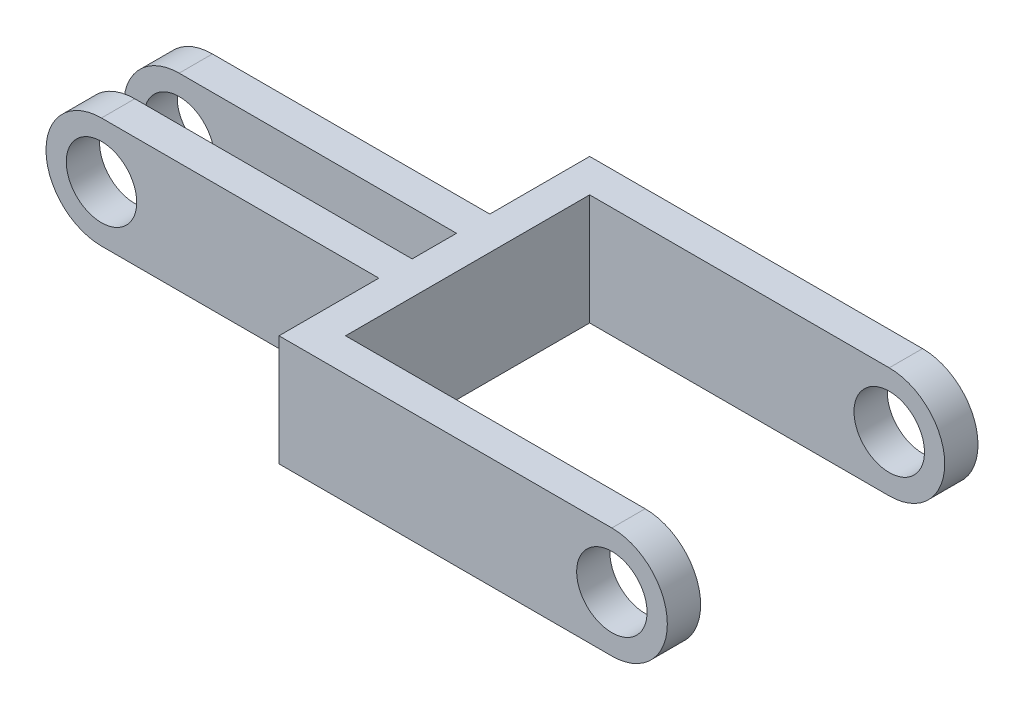
SolidWorks part; units mm, degrees
ref_plane "Front Plane" through (0, 0, 0) normal (0, 0, 1) x (1, 0, 0)
ref_plane "Top Plane" through (0, 0, 0) normal (0, 1, 0) x (1, 0, 0)
ref_plane "Right Plane" through (0, 0, 0) normal (1, 0, 0) x (0, 0, -1)
sketch "Sketch1" plane through (0, 0, 0) normal (0, 0, 1) x (1, 0, 0)
  line L0 (12.5, 10) -> (12.5, 0) construction
  line L1 (0, 0) -> (25, 0)
  line L3 (0, 10) -> (25, 10)
  line L4 (25, 10) -> (25, 0)
  arc A0 (0, 10) -> (0, 0) centre (0, 5) ccw
  circle A2 centre (0, 5) radius 3.175
  dimension "D3" = 6.35
  dimension "D1" = 10
  dimension "D2" = 25
extrude "Boss-Extrude1" add sketch "Sketch1" along normal blind 3
sketch "Sketch2" plane through (25, 0, 0) normal (1, 0, 0) x (0, 0, -1)
  line L1 (-3, 0) -> (6, 0)
  line L2 (-3, 0) -> (-3, 10)
  line L3 (-3, 10) -> (6, 10)
  line L4 (6, 0) -> (6, 10)
  dimension "D1" = 9
  dimension "D2" = 10
extrude "Boss-Extrude2" add sketch "Sketch2" along normal blind 3
sketch "Sketch3" plane through (0, 0, -6) normal (0, 0, -1) x (-1, 0, 0)
  line L0 (-28, 10) -> (-25, 10) construction
  line L1 (-25, 0) -> (-55, 0)
  line L2 (-25, 0) -> (-25, 10)
  line L3 (-25, 10) -> (-55, 10)
  line L4 (-55, 0) -> (-55, 10)
  dimension "D1" = 30
extrude "Boss-Extrude3" add sketch "Sketch3" along normal blind 3
ref_plane "Plane1" through (0, 0, 1.5) normal (0, 0, -1) x (-1, 0, 0)
sketch "Sketch5" plane through (0, 0, -9) normal (0, 0, -1) x (-1, 0, 0)
  line L0 (-55, 10) -> (-55, 0)
  arc A0 (-55, 10) -> (-55, 0) centre (-55, 5) ccw
extrude "Boss-Extrude4" add sketch "Sketch5" against normal up to surface (3 mm away) up to face at (41.5, 5, -6)
sketch "Sketch6" plane through (0, 0, -9) normal (0, 0, -1) x (-1, 0, 0)
  circle A0 centre (-55, 5) radius 3.175
  dimension "D1" = 6.35
extrude "Cut-Extrude1" cut sketch "Sketch6" against normal blind 3
ref_plane "Plane2" through (0, 0, 5) normal (0, 0, 1) x (1, 0, 0)
sketch "Sketch7" plane through (0, 10, 0) normal (0, 1, 0) x (1, 0, 0)
  line L1 (28, -3) -> (25, -3)
  line L2 (28, -3) -> (28, -11)
  line L3 (28, -11) -> (25, -11)
  line L4 (25, -3) -> (25, -11)
  dimension "D1" = 8
  dimension "D2" = 3
extrude "Boss-Extrude5" add sketch "Sketch7" against normal up to surface (10 mm away) up to face at (27, 0, -3)
mirror "Mirror5" about plane through (0, 0, 5) normal (0, 0, 1) of "Cut-Extrude1", "Boss-Extrude1", "Boss-Extrude3", "Boss-Extrude4", "Boss-Extrude2", "Boss-Extrude5"
ref_axis "Axis1" through (55, 5, 20.3377) along (0, 0, -1)
ref_axis "Axis2" through (0, 5, 0.0769) along (0, 0, 1)
